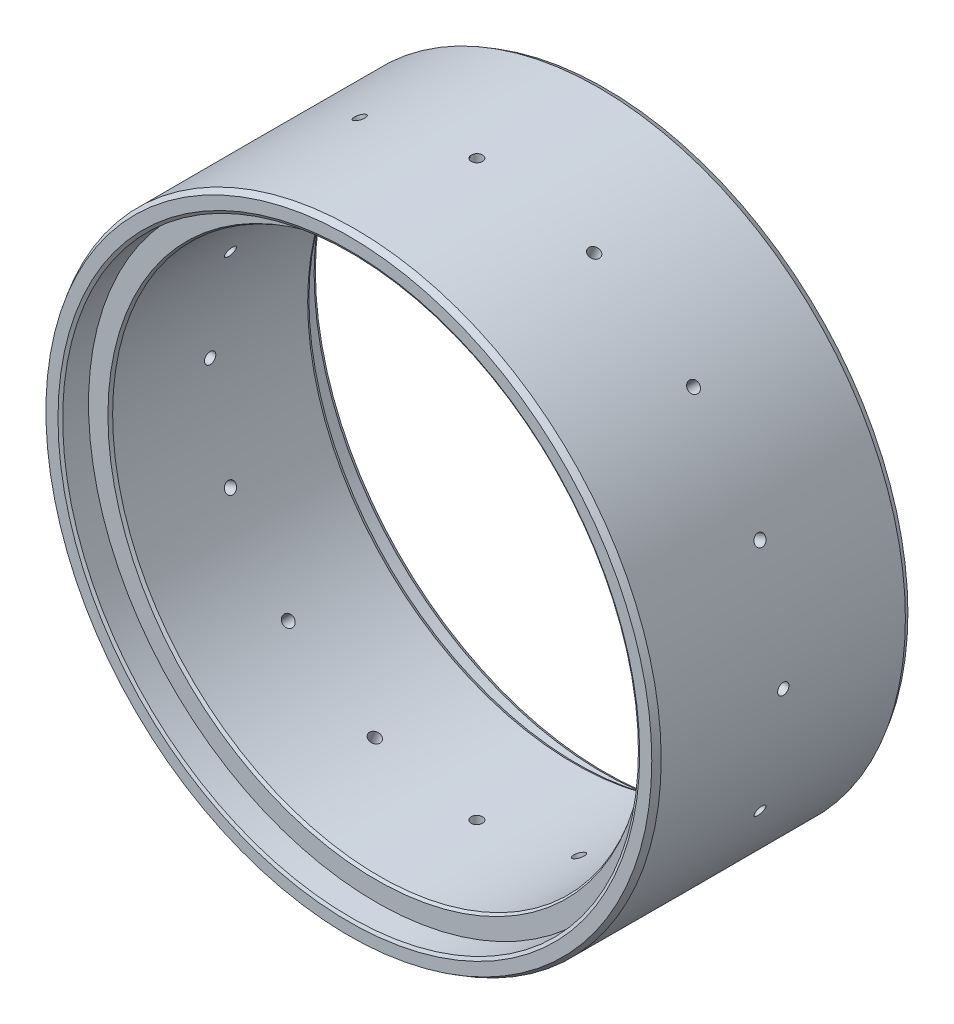
SolidWorks part; units mm, degrees
material "6061-T6 (SS)"
ref_plane "Front Plane" through (0, 0, 0) normal (0, 0, 1) x (1, 0, 0)
ref_plane "Top Plane" through (0, 0, 0) normal (0, 1, 0) x (1, 0, 0)
ref_plane "Right Plane" through (0, 0, 0) normal (1, 0, 0) x (0, 0, -1)
sketch "Sketch1" plane through (0, 0, 0) normal (0, 0, 1) x (1, 0, 0)
  circle A0 centre (0, 0) radius 67.7545
  circle A1 centre (0, 0) radius 58.9915
  dimension "D1" = 135.509
  dimension "D2" = 8.763
extrude "Extrude1" add sketch "Sketch1" along normal mid plane 56.642
sketch "Sketch11" plane through (0, 0, -28.321) normal (0, 0, -1) x (-1, 0, 0)
  circle A0 centre (0, 0) radius 63.66
  dimension "D1" = 127.32
extrude "Extrude2" cut sketch "Sketch11" against normal blind 6.096
mirror "Mirror1" about plane through (0, 0, 0) normal (0, 0, 1) of "Extrude2"
sketch "Sketch2" plane through (0, 0, 0) normal (0, 0, 1) x (1, 0, 0)
  line L0 (0, 0) -> (0, 67.7545) construction
  line L1 (0, 0) -> (13.2182, 66.4526) construction
  circle A0 centre (0, 0) radius 67.7545 construction
  dimension "D1" = 11.25
ref_plane "Plane1" through (0, 67.7545, 0) normal (0, 1, 0) x (-1, 0, 0)
ref_plane "Plane2" through (13.2182, 66.4526, 0) normal (0.1951, 0.9808, 0) x (-0.9808, 0.1951, 0)
sketch "Sketch3" plane through (0, 67.7545, 0) normal (0, 1, 0) x (-1, 0, 0)
  line L0 (0, 0) -> (0, 28.321) construction
  line L1 (0, 28.321) -> (0, -28.321) construction
  line L2 (67.7545, 28.321) -> (-67.7545, 28.321) construction
  point P7 (0, 14.1605)
sketch "Sketch6" plane through (13.2182, 66.4526, 0) normal (0.1951, 0.9808, 0) x (-0.9808, 0.1951, 0)
  line L0 (0, 0) -> (0, 28.321) construction
  line L1 (67.7545, 28.321) -> (-67.7545, 28.321) construction
  point P5 (0, 14.1605)
hole_wizard "Tap Drill for M3x0.5 Tap1" positions "Sketch5" profile "Sketch4" hole size "M3x0.5" standard "Ansi Metric"
sketch "Sketch5" plane through (0, 67.7545, 0) normal (0, 1, 0) x (-1, 0, 0)
  point P6 (0, 0)
sketch "Sketch4" plane through (0, 67.7545, 0) normal (1, 0, 0) x (0, 0, 1)
  line L0 (0, 0) -> (0, 10.9111)
  line L1 (0, 10.9111) -> (1.25, 10.16)
  line L2 (1.25, 10.16) -> (1.25, 0)
  line L5 (1.25, 0) -> (0, 0)
  line L10 (0, 10.9111) -> (-1.25, 10.16) construction
  line L11 (0, -6.35) -> (0, 107.95) construction
  dimension "Hole Dia." = 2.5
  dimension "Hole Depth" = 10.16
  dimension "Drill Angle" = 118
pattern_circular "CirPattern1" count 16 over 360 about axis through (0, 0, 28.321) along (0, 0, -1) of "Tap Drill for M3x0.5 Tap1"
chamfer "Chamfer1" distance 0.381 angle 60 4 edges at (-58.9915, 0, -22.225) (-63.66, 0, 28.321) (58.9915, 0, 22.225) (-63.66, 0, -28.321) first distance on face at (-58.9915, 0, -22.225) first distance on face at (-63.66, 0, 22.225) first distance on face at (58.9915, 0, 22.225) first distance on face at (-63.66, 0, -28.321)
chamfer "Chamfer3" distance 0.762 angle 60 2 edges at (67.7545, 0, 28.321) (67.7545, 0, -28.321) first distance on face at (64.3199, 0, 28.321) first distance on face at (64.041, 0, -28.321)
